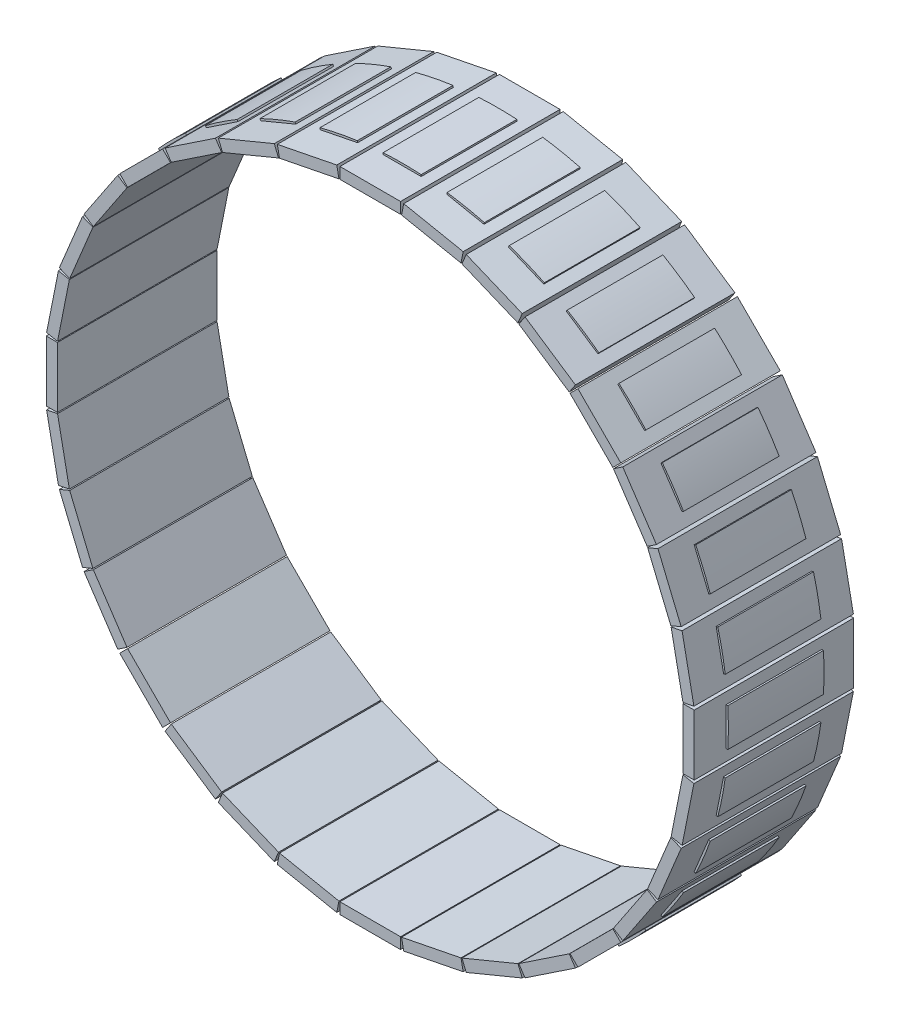
SolidWorks part; units mm, degrees
material "Никель"
ref_plane "Спереди" through (0, 0, 0) normal (0, 0, 1) x (1, 0, 0)
ref_plane "Сверху" through (0, 0, 0) normal (0, 1, 0) x (1, 0, 0)
ref_plane "Справа" through (0, 0, 0) normal (1, 0, 0) x (0, 0, -1)
sketch "Эскиз1" plane through (0, 0, 0) normal (0, 0, 1) x (1, 0, 0)
  line L1 (-9.5, 101.5566) -> (9.5, 101.5566)
  line L2 (-9.5, 101.5566) -> (-9.5, 98.0566)
  line L3 (-9.5, 98.0566) -> (9.5, 98.0566)
  line L4 (9.5, 101.5566) -> (9.5, 98.0566)
  line L5 (0, 98.0566) -> (0, 101.5566) construction
  line L6 (-9.5, 99.8066) -> (9.5, 99.8066) construction
  line L130 (10.4953, 101.4586) -> (9.8124, 98.0259)
  line L131 (10.4953, 101.4586) -> (29.1302, 97.7519)
  line L132 (29.1302, 97.7519) -> (28.4474, 94.3191)
  line L133 (9.8124, 98.0259) -> (28.4474, 94.3191)
  line L134 (30.0872, 97.4616) -> (28.7478, 94.228)
  line L135 (30.0872, 97.4616) -> (47.6409, 90.1906)
  line L136 (47.6409, 90.1906) -> (46.3015, 86.957)
  line L137 (28.7478, 94.228) -> (46.3015, 86.957)
  line L138 (48.5229, 89.7192) -> (46.5784, 86.809)
  line L139 (48.5229, 89.7192) -> (64.3208, 79.1633)
  line L140 (64.3208, 79.1633) -> (62.3763, 76.2532)
  line L141 (46.5784, 86.809) -> (62.3763, 76.2532)
  line L142 (65.0939, 78.5289) -> (62.619, 76.054)
  line L143 (65.0939, 78.5289) -> (78.5289, 65.0939)
  line L144 (78.5289, 65.0939) -> (76.054, 62.619)
  line L145 (62.619, 76.054) -> (76.054, 62.619)
  line L146 (79.1633, 64.3208) -> (76.2532, 62.3763)
  line L147 (79.1633, 64.3208) -> (89.7192, 48.5229)
  line L148 (89.7192, 48.5229) -> (86.809, 46.5784)
  line L149 (76.2532, 62.3763) -> (86.809, 46.5784)
  line L150 (90.1906, 47.6409) -> (86.957, 46.3015)
  line L151 (90.1906, 47.6409) -> (97.4616, 30.0872)
  line L152 (97.4616, 30.0872) -> (94.228, 28.7478)
  line L153 (86.957, 46.3015) -> (94.228, 28.7478)
  line L154 (97.7519, 29.1302) -> (94.3191, 28.4474)
  line L155 (97.7519, 29.1302) -> (101.4586, 10.4953)
  line L156 (101.4586, 10.4953) -> (98.0259, 9.8124)
  line L157 (94.3191, 28.4474) -> (98.0259, 9.8124)
  line L158 (101.5566, 9.5) -> (98.0566, 9.5)
  line L159 (101.5566, 9.5) -> (101.5566, -9.5)
  line L160 (101.5566, -9.5) -> (98.0566, -9.5)
  line L161 (98.0566, 9.5) -> (98.0566, -9.5)
  line L162 (101.4586, -10.4953) -> (98.0259, -9.8124)
  line L163 (101.4586, -10.4953) -> (97.7519, -29.1302)
  line L164 (97.7519, -29.1302) -> (94.3191, -28.4474)
  line L165 (98.0259, -9.8124) -> (94.3191, -28.4474)
  line L166 (97.4616, -30.0872) -> (94.228, -28.7478)
  line L167 (97.4616, -30.0872) -> (90.1906, -47.6409)
  line L168 (90.1906, -47.6409) -> (86.957, -46.3015)
  line L169 (94.228, -28.7478) -> (86.957, -46.3015)
  line L170 (89.7192, -48.5229) -> (86.809, -46.5784)
  line L171 (89.7192, -48.5229) -> (79.1633, -64.3208)
  line L172 (79.1633, -64.3208) -> (76.2532, -62.3763)
  line L173 (86.809, -46.5784) -> (76.2532, -62.3763)
  line L174 (78.5289, -65.0939) -> (76.054, -62.619)
  line L175 (78.5289, -65.0939) -> (65.0939, -78.5289)
  line L176 (65.0939, -78.5289) -> (62.619, -76.054)
  line L177 (76.054, -62.619) -> (62.619, -76.054)
  line L178 (64.3208, -79.1633) -> (62.3763, -76.2532)
  line L179 (64.3208, -79.1633) -> (48.5229, -89.7192)
  line L180 (48.5229, -89.7192) -> (46.5784, -86.809)
  line L181 (62.3763, -76.2532) -> (46.5784, -86.809)
  line L182 (47.6409, -90.1906) -> (46.3015, -86.957)
  line L183 (47.6409, -90.1906) -> (30.0872, -97.4616)
  line L184 (30.0872, -97.4616) -> (28.7478, -94.228)
  line L185 (46.3015, -86.957) -> (28.7478, -94.228)
  line L186 (29.1302, -97.7519) -> (28.4474, -94.3191)
  line L187 (29.1302, -97.7519) -> (10.4953, -101.4586)
  line L188 (10.4953, -101.4586) -> (9.8124, -98.0259)
  line L189 (28.4474, -94.3191) -> (9.8124, -98.0259)
  line L190 (9.5, -101.5566) -> (9.5, -98.0566)
  line L191 (9.5, -101.5566) -> (-9.5, -101.5566)
  line L192 (-9.5, -101.5566) -> (-9.5, -98.0566)
  line L193 (9.5, -98.0566) -> (-9.5, -98.0566)
  line L194 (-10.4953, -101.4586) -> (-9.8124, -98.0259)
  line L195 (-10.4953, -101.4586) -> (-29.1302, -97.7519)
  line L196 (-29.1302, -97.7519) -> (-28.4474, -94.3191)
  line L197 (-9.8124, -98.0259) -> (-28.4474, -94.3191)
  line L198 (-30.0872, -97.4616) -> (-28.7478, -94.228)
  line L199 (-30.0872, -97.4616) -> (-47.6409, -90.1906)
  line L200 (-47.6409, -90.1906) -> (-46.3015, -86.957)
  line L201 (-28.7478, -94.228) -> (-46.3015, -86.957)
  line L202 (-48.5229, -89.7192) -> (-46.5784, -86.809)
  line L203 (-48.5229, -89.7192) -> (-64.3208, -79.1633)
  line L204 (-64.3208, -79.1633) -> (-62.3763, -76.2532)
  line L205 (-46.5784, -86.809) -> (-62.3763, -76.2532)
  line L206 (-65.0939, -78.5289) -> (-62.619, -76.054)
  line L207 (-65.0939, -78.5289) -> (-78.5289, -65.0939)
  line L208 (-78.5289, -65.0939) -> (-76.054, -62.619)
  line L209 (-62.619, -76.054) -> (-76.054, -62.619)
  line L210 (-79.1633, -64.3208) -> (-76.2532, -62.3763)
  line L211 (-79.1633, -64.3208) -> (-89.7192, -48.5229)
  line L212 (-89.7192, -48.5229) -> (-86.809, -46.5784)
  line L213 (-76.2532, -62.3763) -> (-86.809, -46.5784)
  line L214 (-90.1906, -47.6409) -> (-86.957, -46.3015)
  line L215 (-90.1906, -47.6409) -> (-97.4616, -30.0872)
  line L216 (-97.4616, -30.0872) -> (-94.228, -28.7478)
  line L217 (-86.957, -46.3015) -> (-94.228, -28.7478)
  line L218 (-97.7519, -29.1302) -> (-94.3191, -28.4474)
  line L219 (-97.7519, -29.1302) -> (-101.4586, -10.4953)
  line L220 (-101.4586, -10.4953) -> (-98.0259, -9.8124)
  line L221 (-94.3191, -28.4474) -> (-98.0259, -9.8124)
  line L222 (-101.5566, -9.5) -> (-98.0566, -9.5)
  line L223 (-101.5566, -9.5) -> (-101.5566, 9.5)
  line L224 (-101.5566, 9.5) -> (-98.0566, 9.5)
  line L225 (-98.0566, -9.5) -> (-98.0566, 9.5)
  line L226 (-101.4586, 10.4953) -> (-98.0259, 9.8124)
  line L227 (-101.4586, 10.4953) -> (-97.7519, 29.1302)
  line L228 (-97.7519, 29.1302) -> (-94.3191, 28.4474)
  line L229 (-98.0259, 9.8124) -> (-94.3191, 28.4474)
  line L230 (-97.4616, 30.0872) -> (-94.228, 28.7478)
  line L231 (-97.4616, 30.0872) -> (-90.1906, 47.6409)
  line L232 (-90.1906, 47.6409) -> (-86.957, 46.3015)
  line L233 (-94.228, 28.7478) -> (-86.957, 46.3015)
  line L234 (-89.7192, 48.5229) -> (-86.809, 46.5784)
  line L235 (-89.7192, 48.5229) -> (-79.1633, 64.3208)
  line L236 (-79.1633, 64.3208) -> (-76.2532, 62.3763)
  line L237 (-86.809, 46.5784) -> (-76.2532, 62.3763)
  line L238 (-78.5289, 65.0939) -> (-76.054, 62.619)
  line L239 (-78.5289, 65.0939) -> (-65.0939, 78.5289)
  line L240 (-65.0939, 78.5289) -> (-62.619, 76.054)
  line L241 (-76.054, 62.619) -> (-62.619, 76.054)
  line L242 (-64.3208, 79.1633) -> (-62.3763, 76.2532)
  line L243 (-64.3208, 79.1633) -> (-48.5229, 89.7192)
  line L244 (-48.5229, 89.7192) -> (-46.5784, 86.809)
  line L245 (-62.3763, 76.2532) -> (-46.5784, 86.809)
  line L246 (-47.6409, 90.1906) -> (-46.3015, 86.957)
  line L247 (-47.6409, 90.1906) -> (-30.0872, 97.4616)
  line L248 (-30.0872, 97.4616) -> (-28.7478, 94.228)
  line L249 (-46.3015, 86.957) -> (-28.7478, 94.228)
  line L250 (-29.1302, 97.7519) -> (-28.4474, 94.3191)
  line L251 (-29.1302, 97.7519) -> (-10.4953, 101.4586)
  line L252 (-10.4953, 101.4586) -> (-9.8124, 98.0259)
  line L253 (-28.4474, 94.3191) -> (-9.8124, 98.0259)
  circle A0 centre (0, 0) radius 102 construction
  point P3 (0, 99.8066)
  point P139 (-0.2511, -0.2511)
  point P140 (0, 0)
  dimension "D1" = 204
  dimension "D2" = 32
  dimension "D3" = 19
extrude "Бобышка-Вытянуть1" add sketch "Эскиз1" along normal blind 50
sketch "Эскиз2" plane through (0, 0, 50) normal (0, 0, 1) x (1, 0, 0)
  line L0 (-5.9657, 102.0758) -> (-5.9657, 100.5331)
  line L1 (-5.9657, 100.5331) -> (5.9657, 100.5331)
  line L2 (5.9657, 100.5331) -> (5.9657, 102.0758)
  line L3 (0, 98.0566) -> (0, 105.2003) construction
  line L4 (-9.5, 98.0566) -> (9.5, 98.0566) construction
  line L5 (25.4641, 97.4375) -> (25.7651, 98.9506)
  line L6 (14.0629, 101.2783) -> (13.762, 99.7652)
  line L7 (13.762, 99.7652) -> (25.4641, 97.4375)
  line L8 (43.9839, 90.5975) -> (44.5743, 92.0228)
  line L9 (33.5511, 96.5887) -> (32.9608, 95.1634)
  line L10 (32.9608, 95.1634) -> (43.9839, 90.5975)
  line L11 (60.8135, 80.2758) -> (61.6706, 81.5586)
  line L12 (51.75, 88.1873) -> (50.8929, 86.9046)
  line L13 (50.8929, 86.9046) -> (60.8135, 80.2758)
  line L14 (75.306, 66.8692) -> (76.3969, 67.9601)
  line L15 (67.9601, 76.3969) -> (66.8692, 75.306)
  line L16 (66.8692, 75.306) -> (75.306, 66.8692)
  line L17 (86.9046, 50.8929) -> (88.1873, 51.75)
  line L18 (81.5586, 61.6706) -> (80.2758, 60.8135)
  line L19 (80.2758, 60.8135) -> (86.9046, 50.8929)
  line L20 (95.1634, 32.9608) -> (96.5887, 33.5511)
  line L21 (92.0228, 44.5743) -> (90.5975, 43.9839)
  line L22 (90.5975, 43.9839) -> (95.1634, 32.9608)
  line L23 (99.7652, 13.762) -> (101.2783, 14.0629)
  line L24 (98.9506, 25.7651) -> (97.4375, 25.4641)
  line L25 (97.4375, 25.4641) -> (99.7652, 13.762)
  line L26 (100.5331, -5.9657) -> (102.0758, -5.9657)
  line L27 (102.0758, 5.9657) -> (100.5331, 5.9657)
  line L28 (100.5331, 5.9657) -> (100.5331, -5.9657)
  line L29 (97.4375, -25.4641) -> (98.9506, -25.7651)
  line L30 (101.2783, -14.0629) -> (99.7652, -13.762)
  line L31 (99.7652, -13.762) -> (97.4375, -25.4641)
  line L32 (90.5975, -43.9839) -> (92.0228, -44.5743)
  line L33 (96.5887, -33.5511) -> (95.1634, -32.9608)
  line L34 (95.1634, -32.9608) -> (90.5975, -43.9839)
  line L35 (80.2758, -60.8135) -> (81.5586, -61.6706)
  line L36 (88.1873, -51.75) -> (86.9046, -50.8929)
  line L37 (86.9046, -50.8929) -> (80.2758, -60.8135)
  line L38 (66.8692, -75.306) -> (67.9601, -76.3969)
  line L39 (76.3969, -67.9601) -> (75.306, -66.8692)
  line L40 (75.306, -66.8692) -> (66.8692, -75.306)
  line L41 (50.8929, -86.9046) -> (51.75, -88.1873)
  line L42 (61.6706, -81.5586) -> (60.8135, -80.2758)
  line L43 (60.8135, -80.2758) -> (50.8929, -86.9046)
  line L44 (32.9608, -95.1634) -> (33.5511, -96.5887)
  line L45 (44.5743, -92.0228) -> (43.9839, -90.5975)
  line L46 (43.9839, -90.5975) -> (32.9608, -95.1634)
  line L47 (13.762, -99.7652) -> (14.0629, -101.2783)
  line L48 (25.7651, -98.9506) -> (25.4641, -97.4375)
  line L49 (25.4641, -97.4375) -> (13.762, -99.7652)
  line L50 (-5.9657, -100.5331) -> (-5.9657, -102.0758)
  line L51 (5.9657, -102.0758) -> (5.9657, -100.5331)
  line L52 (5.9657, -100.5331) -> (-5.9657, -100.5331)
  line L53 (-25.4641, -97.4375) -> (-25.7651, -98.9506)
  line L54 (-14.0629, -101.2783) -> (-13.762, -99.7652)
  line L55 (-13.762, -99.7652) -> (-25.4641, -97.4375)
  line L56 (-43.9839, -90.5975) -> (-44.5743, -92.0228)
  line L57 (-33.5511, -96.5887) -> (-32.9608, -95.1634)
  line L58 (-32.9608, -95.1634) -> (-43.9839, -90.5975)
  line L59 (-60.8135, -80.2758) -> (-61.6706, -81.5586)
  line L60 (-51.75, -88.1873) -> (-50.8929, -86.9046)
  line L61 (-50.8929, -86.9046) -> (-60.8135, -80.2758)
  line L62 (-75.306, -66.8692) -> (-76.3969, -67.9601)
  line L63 (-67.9601, -76.3969) -> (-66.8692, -75.306)
  line L64 (-66.8692, -75.306) -> (-75.306, -66.8692)
  line L65 (-86.9046, -50.8929) -> (-88.1873, -51.75)
  line L66 (-81.5586, -61.6706) -> (-80.2758, -60.8135)
  line L67 (-80.2758, -60.8135) -> (-86.9046, -50.8929)
  line L68 (-95.1634, -32.9608) -> (-96.5887, -33.5511)
  line L69 (-92.0228, -44.5743) -> (-90.5975, -43.9839)
  line L70 (-90.5975, -43.9839) -> (-95.1634, -32.9608)
  line L71 (-99.7652, -13.762) -> (-101.2783, -14.0629)
  line L72 (-98.9506, -25.7651) -> (-97.4375, -25.4641)
  line L73 (-97.4375, -25.4641) -> (-99.7652, -13.762)
  line L74 (-100.5331, 5.9657) -> (-102.0758, 5.9657)
  line L75 (-102.0758, -5.9657) -> (-100.5331, -5.9657)
  line L76 (-100.5331, -5.9657) -> (-100.5331, 5.9657)
  line L77 (-97.4375, 25.4641) -> (-98.9506, 25.7651)
  line L78 (-101.2783, 14.0629) -> (-99.7652, 13.762)
  line L79 (-99.7652, 13.762) -> (-97.4375, 25.4641)
  line L80 (-90.5975, 43.9839) -> (-92.0228, 44.5743)
  line L81 (-96.5887, 33.5511) -> (-95.1634, 32.9608)
  line L82 (-95.1634, 32.9608) -> (-90.5975, 43.9839)
  line L83 (-80.2758, 60.8135) -> (-81.5586, 61.6706)
  line L84 (-88.1873, 51.75) -> (-86.9046, 50.8929)
  line L85 (-86.9046, 50.8929) -> (-80.2758, 60.8135)
  line L86 (-66.8692, 75.306) -> (-67.9601, 76.3969)
  line L87 (-76.3969, 67.9601) -> (-75.306, 66.8692)
  line L88 (-75.306, 66.8692) -> (-66.8692, 75.306)
  line L89 (-50.8929, 86.9046) -> (-51.75, 88.1873)
  line L90 (-61.6706, 81.5586) -> (-60.8135, 80.2758)
  line L91 (-60.8135, 80.2758) -> (-50.8929, 86.9046)
  line L92 (-32.9608, 95.1634) -> (-33.5511, 96.5887)
  line L93 (-44.5743, 92.0228) -> (-43.9839, 90.5975)
  line L94 (-43.9839, 90.5975) -> (-32.9608, 95.1634)
  line L95 (-13.762, 99.7652) -> (-14.0629, 101.2783)
  line L96 (-25.7651, 98.9506) -> (-25.4641, 97.4375)
  line L97 (-25.4641, 97.4375) -> (-13.762, 99.7652)
  circle A0 centre (0, 0) radius 102.25 construction
  arc A1 (-5.9657, 102.0758) -> (5.9657, 102.0758) centre (0, 0) cw
  arc A2 (14.0629, 101.2783) -> (25.7651, 98.9506) centre (0, 0) cw
  arc A3 (33.5511, 96.5887) -> (44.5743, 92.0228) centre (0, 0) cw
  arc A4 (51.75, 88.1873) -> (61.6706, 81.5586) centre (0, 0) cw
  arc A5 (67.9601, 76.3969) -> (76.3969, 67.9601) centre (0, 0) cw
  arc A6 (81.5586, 61.6706) -> (88.1873, 51.75) centre (0, 0) cw
  arc A7 (92.0228, 44.5743) -> (96.5887, 33.5511) centre (0, 0) cw
  arc A8 (98.9506, 25.7651) -> (101.2783, 14.0629) centre (0, 0) cw
  arc A9 (102.0758, 5.9657) -> (102.0758, -5.9657) centre (0, 0) cw
  arc A10 (101.2783, -14.0629) -> (98.9506, -25.7651) centre (0, 0) cw
  arc A11 (96.5887, -33.5511) -> (92.0228, -44.5743) centre (0, 0) cw
  arc A12 (88.1873, -51.75) -> (81.5586, -61.6706) centre (0, 0) cw
  arc A13 (76.3969, -67.9601) -> (67.9601, -76.3969) centre (0, 0) cw
  arc A14 (61.6706, -81.5586) -> (51.75, -88.1873) centre (0, 0) cw
  arc A15 (44.5743, -92.0228) -> (33.5511, -96.5887) centre (0, 0) cw
  arc A16 (25.7651, -98.9506) -> (14.0629, -101.2783) centre (0, 0) cw
  arc A17 (5.9657, -102.0758) -> (-5.9657, -102.0758) centre (0, 0) cw
  arc A18 (-14.0629, -101.2783) -> (-25.7651, -98.9506) centre (0, 0) cw
  arc A19 (-33.5511, -96.5887) -> (-44.5743, -92.0228) centre (0, 0) cw
  arc A20 (-51.75, -88.1873) -> (-61.6706, -81.5586) centre (0, 0) cw
  arc A21 (-67.9601, -76.3969) -> (-76.3969, -67.9601) centre (0, 0) cw
  arc A22 (-81.5586, -61.6706) -> (-88.1873, -51.75) centre (0, 0) cw
  arc A23 (-92.0228, -44.5743) -> (-96.5887, -33.5511) centre (0, 0) cw
  arc A24 (-98.9506, -25.7651) -> (-101.2783, -14.0629) centre (0, 0) cw
  arc A25 (-102.0758, -5.9657) -> (-102.0758, 5.9657) centre (0, 0) cw
  arc A26 (-101.2783, 14.0629) -> (-98.9506, 25.7651) centre (0, 0) cw
  arc A27 (-96.5887, 33.5511) -> (-92.0228, 44.5743) centre (0, 0) cw
  arc A28 (-88.1873, 51.75) -> (-81.5586, 61.6706) centre (0, 0) cw
  arc A29 (-76.3969, 67.9601) -> (-67.9601, 76.3969) centre (0, 0) cw
  arc A30 (-61.6706, 81.5586) -> (-51.75, 88.1873) centre (0, 0) cw
  arc A31 (-44.5743, 92.0228) -> (-33.5511, 96.5887) centre (0, 0) cw
  arc A32 (-25.7651, 98.9506) -> (-14.0629, 101.2783) centre (0, 0) cw
  point P12 (0, 100.5331)
  point P140 (0, 0)
  dimension "D1" = 204.5
  dimension "D2" = 32
extrude "Бобышка-Вытянуть2" add sketch "Эскиз2" against normal blind 30 from offset 10 offset against normal yes
